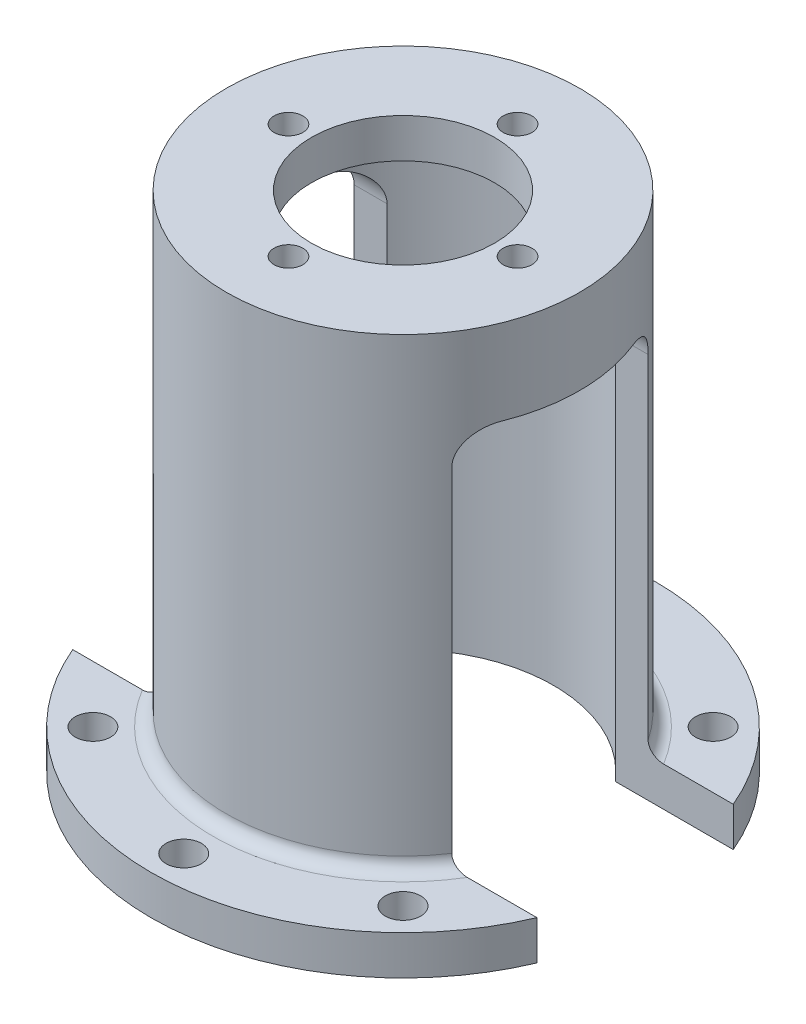
SolidWorks part; units mm, degrees
material "1060 Alloy"
ref_plane "Front Plane" through (0, 0, 0) normal (0, 0, 1) x (1, 0, 0)
ref_plane "Top Plane" through (0, 0, 0) normal (0, 1, 0) x (1, 0, 0)
ref_plane "Right Plane" through (0, 0, 0) normal (1, 0, 0) x (0, 0, -1)
sketch "Sketch1" plane through (0, 0, 0) normal (0, 1, 0) x (1, 0, 0)
  circle A0 centre (0, 0) radius 23
  circle A1 centre (0, 0) radius 27
  dimension "D1" = 46
  dimension "D2" = 54
extrude "Boss-Extrude1" add sketch "Sketch1" along normal blind 77
sketch "Sketch2" plane through (0, 77, 0) normal (0, 1, 0) x (1, 0, 0)
  circle A0 centre (0, 0) radius 27
extrude "Boss-Extrude2" add sketch "Sketch2" against normal blind 6
sketch "Sketch3" plane through (0, 0, 0) normal (0, -1, 0) x (1, 0, 0)
  circle A0 centre (0, 0) radius 23
  circle A1 centre (0, 0) radius 38.5
  dimension "D1" = 77
extrude "Boss-Extrude3" add sketch "Sketch3" against normal blind 6
sketch "Sketch4" plane through (0, 77, 0) normal (0, 1, 0) x (1, 0, 0)
  circle A0 centre (0, 0) radius 14
  dimension "D1" = 28
extrude "Cut-Extrude1" cut sketch "Sketch4" against normal through all
ref_axis "Axis1" through (0, -3.85, 0) along (0, 1, 0)
sketch "Sketch5" plane through (0, 0, 0) normal (1, 0, 0) x (0, 0, -1)
  line L0 (-15, 0) -> (-15, 59)
  line L1 (-23, 0) -> (23, 0) construction
  line L2 (-10, 64) -> (10, 64)
  line L3 (0, -3.85) -> (0, 80.85) construction
  line L4 (-15, 0) -> (15, 0)
  line L5 (0, 0) -> (0, 77) construction
  line L6 (27, 77) -> (-27, 77) construction
  line L7 (15, 0) -> (15, 59)
  arc A0 (-15, 59) -> (-10, 64) centre (-10, 59) cw
  arc A1 (15, 59) -> (10, 64) centre (10, 59) ccw
  point P18 (0, 64)
  dimension "D3" = 5
  dimension "D1" = 15
  dimension "D2" = 64
extrude "Cut-Extrude2" cut sketch "Sketch5" against normal through all both and the other way through all
fillet "Fillet1" radius 2 3 edges at (0, 71, 23) (0, 6, -27) (0, 6, 27)
sketch "Sketch7" plane through (0, 6, 0) normal (0, 1, 0) x (1, 0, 0)
  circle A0 centre (0, 0) radius 33.5 construction
  circle A1 centre (0, 33.5) radius 2.7
  dimension "D1" = 67
  dimension "D2" = 5.4
extrude "Cut-Extrude3" cut sketch "Sketch7" against normal through all
pattern_circular "CirPattern1" count 8 over 360 about axis through (0, -3.85, 0) along (0, 1, 0) skipping 2, 6 of "Cut-Extrude3"
sketch "Sketch8" plane through (0, 77, 0) normal (0, 1, 0) x (1, 0, 0)
  circle A0 centre (0, 0) radius 17.5 construction
  circle A1 centre (0, 17.5) radius 2.2
  dimension "D1" = 35
  dimension "D2" = 4.4
extrude "Cut-Extrude4" cut sketch "Sketch8" against normal through all
pattern_circular "CirPattern2" count 4 over 360 about axis through (0, -3.85, 0) along (0, 1, 0) of "Cut-Extrude4"
